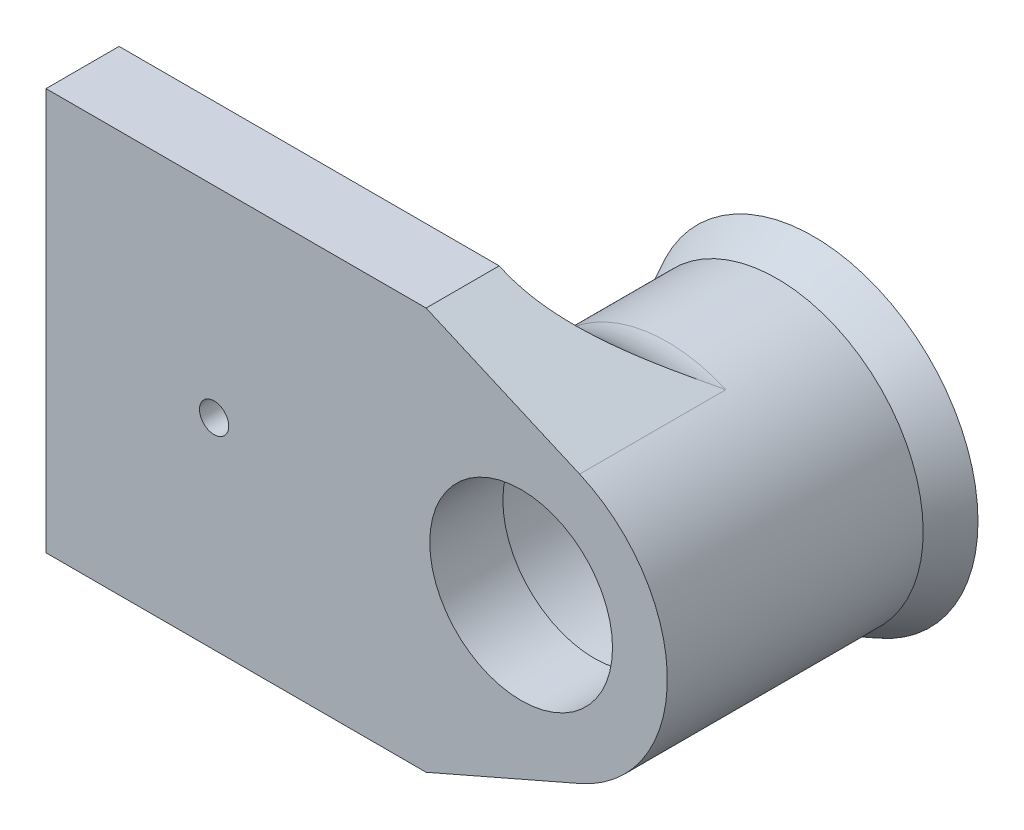
SolidWorks part; units mm, degrees
ref_plane "Front Plane" through (0, 0, 0) normal (0, 0, 1) x (1, 0, 0)
ref_plane "Top Plane" through (0, 0, 0) normal (0, 1, 0) x (1, 0, 0)
ref_plane "Right Plane" through (0, 0, 0) normal (1, 0, 0) x (0, 0, -1)
sketch "Sketch1" plane through (0, 0, 0) normal (0, 0, 1) x (1, 0, 0)
  circle A0 centre (0, 0) radius 15 construction
  circle A1 centre (0, 0) radius 15
  circle A3 centre (0, 0) radius 12.5
  dimension "D1" = 25
extrude "Boss-Extrude1" add sketch "Sketch1" along normal blind 10
sketch "Sketch2" plane through (0, 0, 10) normal (0, 0, 1) x (1, 0, 0)
  line L0 (0, 0) -> (-54.4042, 0) construction
  line L1 (-13, 27.5) -> (-65, 27.5)
  line L3 (-13, -27.5) -> (-65, -27.5)
  line L4 (-65, 27.5) -> (-65, -27.5)
  line L9 (-13, 27.5) -> (8.0033, 18.3288)
  line L16 (-13, -27.5) -> (8.0033, -18.3288)
  circle A0 centre (-42, 0) radius 2
  circle A1 centre (0, 0) radius 12.5
  arc A3 (8.0033, -18.3288) -> (8.0033, 18.3288) centre (0, 0) ccw
  dimension "D4" = 40
  dimension "D6" = 4
  dimension "D7" = 23
  dimension "D1" = 55
  dimension "D2" = 27.5
  dimension "D3" = 65
  dimension "D5" = 13
extrude "Boss-Extrude2" add sketch "Sketch2" against normal blind 10
sketch "Sketch3" plane through (0, 0, 0) normal (0, 0, -1) x (-1, 0, 0)
  circle A0 centre (0, 0) radius 15 construction
  circle A1 centre (0, 0) radius 15
  circle A2 centre (0, 0) radius 20
extrude "Boss-Extrude3" add sketch "Sketch3" along normal blind 25
fillet "Fillet1" radius 10 1 edges at (-20, 0, 0)
ref_plane "Plane1" through (0, 0, -30) normal (0, 0, -1) x (-1, 0, 0)
sketch "Sketch4" plane through (0, 0, -30) normal (0, 0, -1) x (-1, 0, 0)
  circle A0 centre (0, 0) radius 15 construction
  circle A1 centre (0, 0) radius 15
  circle A2 centre (0, 0) radius 22.5
  dimension "D1" = 45
loft "Loft2" add section "Sketch4" section edge at (-20, 0, -25) connector at (18.1696, -13.2709, -30) connector at (16.9755, -10.5751, -25)
sketch "Sketch5" plane through (0, 0, -25) normal (0, 0, 1) x (1, 0, 0)
  circle A1 centre (0, 0) radius 15
  circle A2 centre (0, 0) radius 15
  dimension "D1" = 0
extrude "Cut-Extrude1" cut sketch "Sketch5" against normal through all
